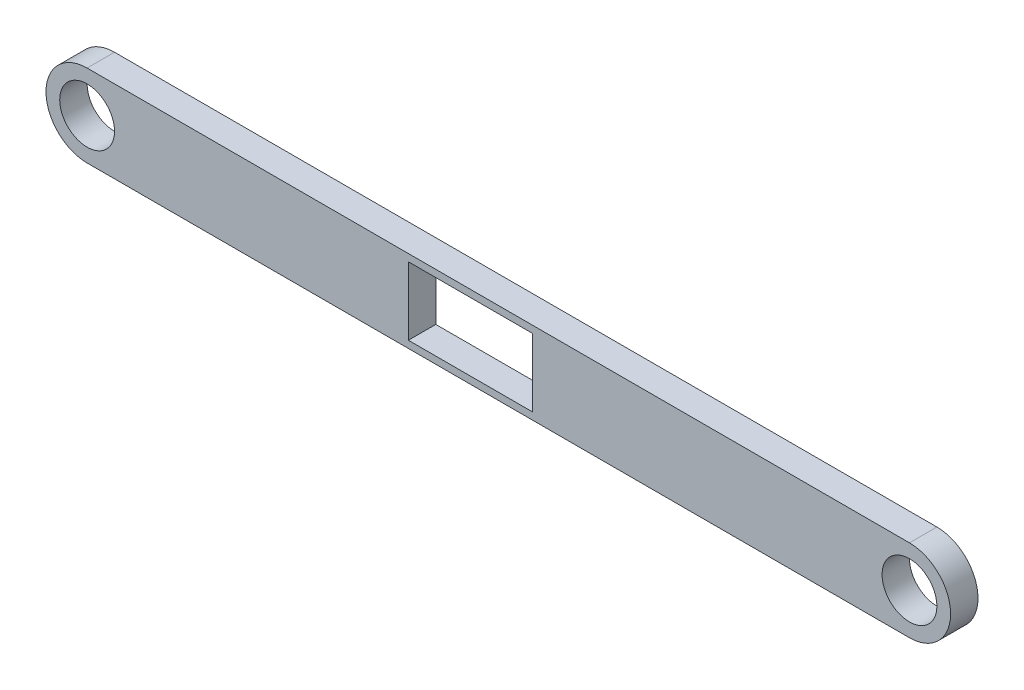
SolidWorks part; units mm, degrees
material "Acrylic (Medium-high impact)"
ref_plane "Front Plane" through (0, 0, 0) normal (0, 0, 1) x (1, 0, 0)
ref_plane "Top Plane" through (0, 0, 0) normal (0, 1, 0) x (1, 0, 0)
ref_plane "Right Plane" through (0, 0, 0) normal (1, 0, 0) x (0, 0, -1)
sketch "Sketch1" plane through (0, 0, 0) normal (0, 0, 1) x (1, 0, 0)
  line L0 (75, 0) -> (-75, 0) construction
  line L1 (75, -7.5) -> (-75, -7.5)
  line L2 (75, 7.5) -> (-75, 7.5)
  line L3 (0, 7.5) -> (0, -7.5) construction
  line L5 (-16.4, 6.2) -> (6.2, 6.2)
  line L6 (-16.4, 6.2) -> (-16.4, -6.2)
  line L7 (-16.4, -6.2) -> (6.2, -6.2)
  line L8 (6.2, 6.2) -> (6.2, -6.2)
  line L9 (-16.4, 6.2) -> (6.2, -6.2) construction
  line L10 (-16.4, -6.2) -> (6.2, 6.2) construction
  arc A0 (75, -7.5) -> (75, 7.5) centre (75, 0) ccw
  arc A1 (-75, 7.5) -> (-75, -7.5) centre (-75, 0) ccw
  circle A2 centre (75, 0) radius 5
  circle A3 centre (-75, 0) radius 5
  point P2 (0, 0)
  point P14 (-5.1, 0)
  point P21 (0, 0)
  dimension "D2" = 10
  dimension "D1" = 150
  dimension "D3" = 15
  dimension "D4" = 22.6
  dimension "D5" = 12.4
  dimension "D6" = 6.2
extrude "Boss-Extrude1" add sketch "Sketch1" along normal blind 5
